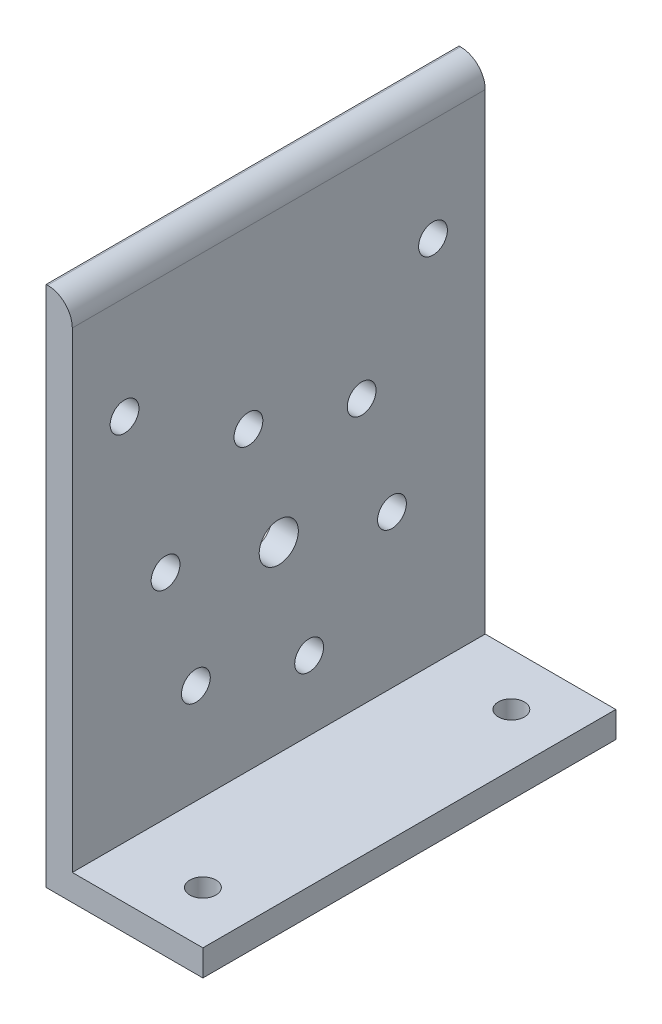
SolidWorks part; units mm, degrees
ref_plane "Front Plane" through (0, 0, 0) normal (0, 0, 1) x (1, 0, 0)
ref_plane "Top Plane" through (0, 0, 0) normal (0, 1, 0) x (1, 0, 0)
ref_plane "Right Plane" through (0, 0, 0) normal (1, 0, 0) x (0, 0, -1)
sketch "Sketch1" plane through (0, 0, 0) normal (0, 0, 1) x (1, 0, 0)
  line L2 (0, 0) -> (0, 127)
  line L3 (0, 127) -> (0.35, 127)
  line L4 (6.35, 37.75) -> (6.35, 121)
  line L6 (0, 0) -> (0, 6.35)
  line L8 (38.1, 0) -> (38.1, 0.35)
  line L9 (6.35, 6.35) -> (6.35, 37.75)
  line L11 (32.1, 6.35) -> (38.1, 6.35)
  line L12 (38.1, 6.35) -> (38.1, 0.35)
  line L13 (38.1, 0) -> (0, 0)
  line L14 (6.35, 6.35) -> (32.1, 6.35)
  arc A1 (0.35, 127) -> (6.35, 121) centre (0.35, 121) cw
  point P10 (38.1, 6.35)
  point P13 (6.35, 127)
  dimension "D1" = 127
  dimension "D2" = 38.1
  dimension "D3" = 6.35
  dimension "D4" = 6.35
extrude "Boss-Extrude1" add sketch "Sketch1" along normal blind 100.4 contours L4 A1 L3 L2 L8 region at (1.3259, 3.175, 0)
sketch "Sketch2" plane through (0, 0, 0) normal (-1, 0, 0) x (0, 0, 1)
  line L0 (50.2, 127) -> (50.2, 0)
  line L1 (57.5763, 78.3289) -> (50.2, 50.8)
  line L3 (100.4, 50.8) -> (0, 50.8) construction
  line L4 (100.4, 0) -> (100.4, 127) construction
  line L5 (0, 0) -> (0, 127) construction
  line L6 (100.4, 0) -> (0, 0) construction
  line L7 (100.4, 127) -> (0, 127) construction
  circle A9 centre (50.2, 50.8) radius 4.7625
  circle A17 centre (57.5763, 78.3289) radius 3.5
  circle A25 centre (50.2, 50.8) radius 28.5
  circle A26 centre (77.7289, 58.1763) radius 3.5
  circle A27 centre (70.3525, 30.6475) radius 3.5
  circle A28 centre (42.8237, 23.2711) radius 3.5
  circle A29 centre (22.6711, 43.4237) radius 3.5
  circle A30 centre (30.0475, 70.9525) radius 3.5
  dimension "D1" = 57
  dimension "D2" = 15
  dimension "D4" = 9.525
  dimension "D5" = 6
  dimension "D6" = 7
  dimension "D3" = 50.8
extrude "Cut-Extrude1" cut sketch "Sketch2" against normal through all both and the other way through all contours A9 | A17 | A26 | A30 | A27 | A28 | A29
sketch "Sketch3" plane through (0, 6.35, 0) normal (0, 1, 0) x (1, 0, 0)
  line L0 (25.4, -100.4) -> (25.4, 0) construction
  line L4 (6.35, -100.4) -> (38.1, -100.4) construction
  line L5 (6.35, 0) -> (38.1, 0) construction
  line L6 (0, -100.4) -> (0, 0) construction
  circle A0 centre (25.4, -12.7) radius 3.175
  circle A2 centre (25.4, -87.7) radius 3.175
  dimension "D2" = 6.35
  dimension "D3" = 12.7
  dimension "D4" = 12.7
  dimension "D5" = 6.35
  dimension "D1" = 25.4
extrude "Cut-Extrude2" cut sketch "Sketch3" against normal through all
ref_plane "Width Centerline Plane" through (0, 0, 50.2) normal (0, 0, 1) x (1, 0, 0)
sketch "Sketch5" plane through (6.35, 0, 0) normal (1, 0, 0) x (0, 0, -1)
  line L0 (-50.2, 6.35) -> (-50.2, 121) construction
  line L1 (-100.4, 121) -> (0, 121) construction
  line L2 (-100.4, 6.35) -> (0, 6.35) construction
  line L3 (-100.4, 6.35) -> (-100.4, 121) construction
  circle A0 centre (-87.7, 96) radius 3.5
  circle A2 centre (-12.7, 96) radius 3.5
  dimension "D1" = 7
  dimension "D2" = 25
  dimension "D3" = 12.7
extrude "Cut-Extrude4" cut sketch "Sketch5" against normal blind 10
